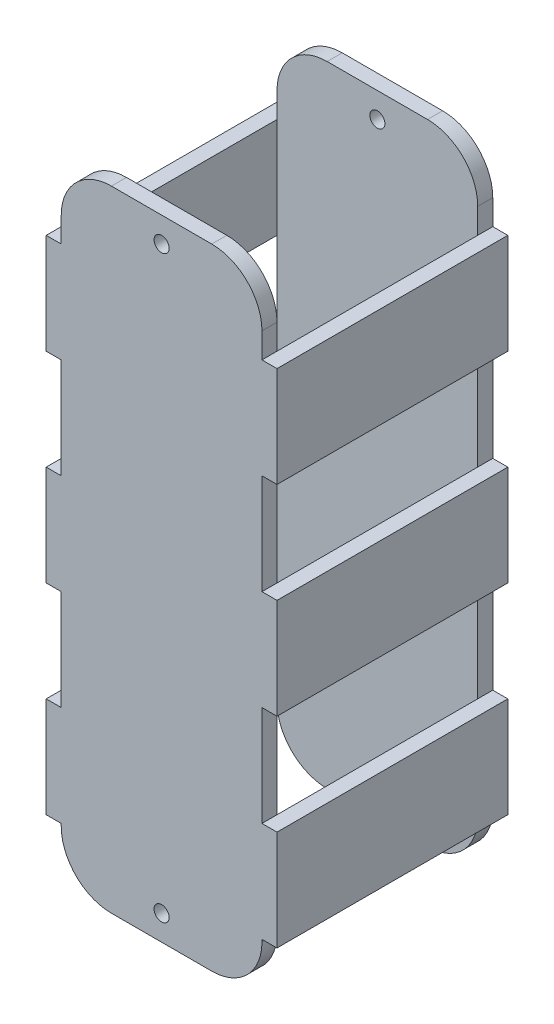
SolidWorks part; units mm, degrees
material "ENPH 253 Hardboard"
ref_plane "Front Plane" through (0, 0, 0) normal (0, 0, 1) x (1, 0, 0)
ref_plane "Top Plane" through (0, 0, 0) normal (0, 1, 0) x (1, 0, 0)
ref_plane "Right Plane" through (0, 0, 0) normal (1, 0, 0) x (0, 0, -1)
sketch "Sketch1" plane through (0, 0, 0) normal (0, 0, 1) x (1, 0, 0)
  line L1 (-10, 62.75) -> (10, 62.75)
  line L2 (-20, 52.75) -> (-20, -52.75)
  line L3 (-10, -62.75) -> (10, -62.75)
  line L4 (20, 52.75) -> (20, -52.75)
  line L5 (-20, 62.75) -> (20, -62.75) construction
  line L6 (-20, -62.75) -> (20, 62.75) construction
  arc A0 (10, -62.75) -> (20, -52.75) centre (10, -52.75) ccw
  arc A1 (-20, -52.75) -> (-10, -62.75) centre (-10, -52.75) ccw
  arc A2 (10, 62.75) -> (20, 52.75) centre (10, 52.75) cw
  arc A3 (-20, 52.75) -> (-10, 62.75) centre (-10, 52.75) cw
  point P0 (0, 0)
  dimension "D3" = 10
  dimension "D1" = 40
  dimension "D2" = 125.5
extrude "Boss-Extrude1" add sketch "Sketch1" along normal blind 3 from offset 40 contours L4 A0 L3 A1 L2 A3 L1 A2
extrude "Boss-Extrude2" add sketch "Sketch1<3>" against normal blind 3 separate body
sketch "Sketch1<3>" plane through (0, 0, 0) normal (0, 0, 1) x (1, 0, 0) same geometry as "Sketch1"
sketch "Sketch2" plane through (0, 0, 0) normal (0, 0, 1) x (1, 0, 0)
  line L0 (55, 0) -> (-55, 0) construction
  line L1 (-10, 62.75) -> (10, 62.75) construction
  circle A0 centre (0, 57.75) radius 1.5
  circle A1 centre (0, -57.75) radius 1.5
  dimension "D2" = 3
  dimension "D1" = 5
extrude "Cut-Extrude1" cut sketch "Sketch2" against normal through all both and the other way through all
sketch "Sketch3" plane through (-20, 0, 0) normal (-1, 0, 0) x (0, 0, 1)
  line L0 (-3, 52.75) -> (-3, -52.75) construction
  line L1 (-3, 47.75) -> (43, 47.75)
  line L2 (-3, 47.75) -> (-3, 27.75)
  line L3 (-3, 27.75) -> (43, 27.75)
  line L4 (43, 47.75) -> (43, 27.75)
  line L5 (43, 52.75) -> (43, -52.75) construction
  line L6 (43, 62.75) -> (40, 62.75) construction
  line L7 (-3, 7.75) -> (-3, -12.25)
  line L8 (-3, 7.75) -> (43, 7.75)
  line L9 (43, 7.75) -> (43, -12.25)
  line L10 (-3, -12.25) -> (43, -12.25)
  line L11 (-3, -32.25) -> (-3, -52.25)
  line L12 (-3, -32.25) -> (43, -32.25)
  line L13 (43, -32.25) -> (43, -52.25)
  line L14 (-3, -52.25) -> (43, -52.25)
  dimension "D1" = 20
  dimension "D2" = 15
  dimension "D3" = 3
extrude "Boss-Extrude4" add sketch "Sketch3" along normal blind 3
mirror "Mirror1" about plane through (0, 0, 0) normal (1, 0, 0) of "Boss-Extrude4"
